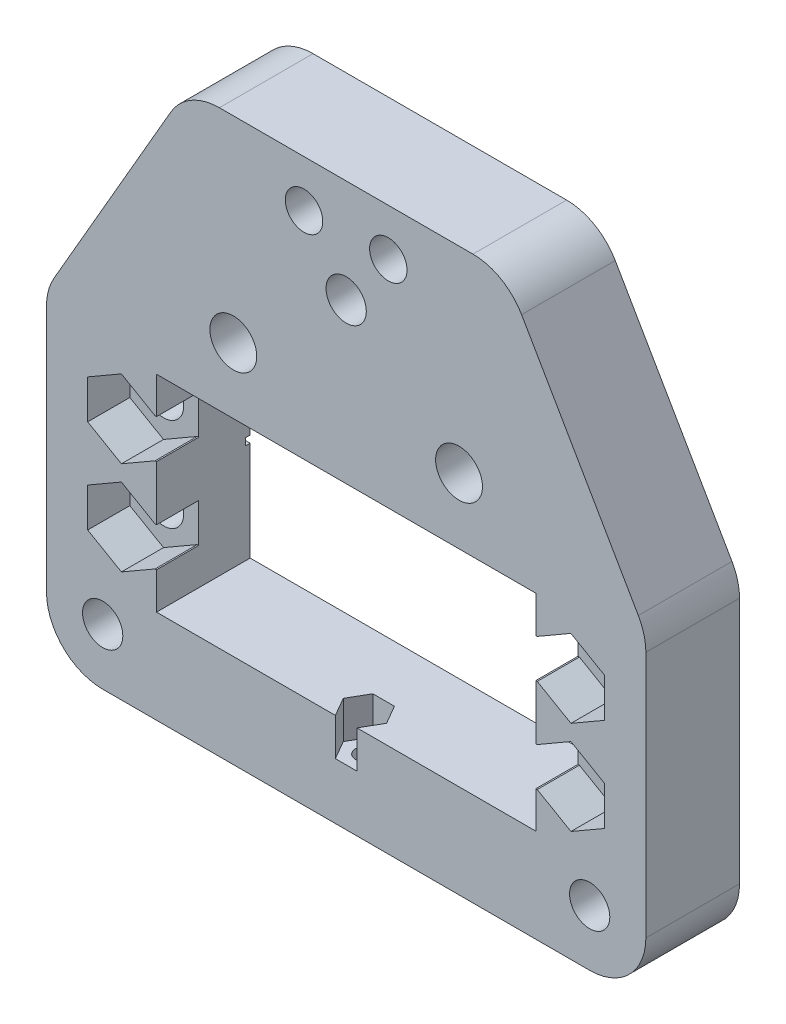
SolidWorks part; units mm, degrees
material "ABS"
ref_plane "Спереди" through (0, 0, 0) normal (0, 0, 1) x (1, 0, 0)
ref_plane "Сверху" through (0, 0, 0) normal (0, 1, 0) x (1, 0, 0)
ref_plane "Справа" through (0, 0, 0) normal (1, 0, 0) x (0, 0, -1)
sketch "Эскиз1" plane through (0, 0, 0) normal (0, 0, 1) x (1, 0, 0)
  line L0 (0, 0) -> (64, 0)
  line L1 (64, 0) -> (64, 34.0192)
  line L2 (64, 34.0192) -> (49, 60)
  line L3 (49, 60) -> (15, 60)
  line L4 (15, 60) -> (0, 34.02)
  line L5 (0, 34.02) -> (0, 0)
  dimension "D1" = 64
  dimension "D2" = 60
  dimension "D3" = 34
  dimension "D4" = 30
  dimension "D5" = 120
  dimension "D6" = 34.02
extrude "Бобышка-Вытянуть1" add sketch "Эскиз1" along normal blind 10 contours L0 L1 L2 L3 L4 L5
fillet "Скругление1" radius 6 6 edges at (49, 60, 5) (15, 60, 5) (0, 34.02, 5) (0, 0, 5) (64, 34.0192, 5) (64, 0, 5)
sketch "Эскиз2" plane through (0, 0, 10) normal (0, 0, 1) x (1, 0, 0)
  line L0 (11.75, 32) -> (52.25, 32)
  line L1 (52.25, 32) -> (52.25, 10)
  line L2 (52.25, 10) -> (11.75, 10)
  line L3 (11.75, 10) -> (11.75, 32)
  line L4 (64, 6) -> (64, 32.4115) construction
  line L5 (6, 0) -> (58, 0) construction
  dimension "D1" = 22
  dimension "D2" = 40.5
  dimension "D3" = 11.75
  dimension "D4" = 10
extrude "Вырез-Вытянуть1" cut sketch "Эскиз2" against normal through all
hole_wizard "Отверстия под штифты Ø4.0 мм1" positions "Эскиз3" profile "Эскиз4" hole size "Ø4.0" standard "Ansi Metric" end condition through all
sketch "Эскиз3" plane through (0, 0, 10) normal (0, 0, 1) x (1, 0, 0)
  line L0 (45.5359, 60) -> (18.4641, 60) construction
  line L1 (64, 6) -> (64, 32.4115) construction
  line L2 (32, 62.7032) -> (32, 49.5714) construction
  point P0 (27.4999, 55)
  point P2 (36.5, 55)
  point P13 (32, 60)
  dimension "D1" = 5
  dimension "D2" = 27.5
sketch "Эскиз4" plane through (27.4999, 55, 10) normal (1, 0, 0) x (0, -1, 0)
  line L0 (0, 0) -> (0, 10)
  line L1 (0, 10) -> (2, 10)
  line L2 (2, 10) -> (2, 0)
  line L5 (2, 0) -> (0, 0)
  line L11 (0, -6.35) -> (0, 13.871) construction
  dimension "Диаметр сквозного отверстия" = 4
  dimension "Глубина сквозного отверстия" = 10
hole_wizard "Отверстия под штифты Ø5.0 мм1" positions "Эскиз5" profile "Эскиз6" hole size "Ø5.0" standard "Ansi Metric" end condition through all
sketch "Эскиз5" plane through (0, 0, 10) normal (0, 0, 1) x (1, 0, 0)
  line L0 (45.5359, 60) -> (18.4641, 60) construction
  line L1 (64, 6) -> (64, 32.4115) construction
  line L2 (32, 62.5774) -> (32, 29.5493) construction
  point P0 (19.9499, 39)
  point P2 (44.05, 39)
  point P13 (32, 60)
  dimension "D1" = 21
  dimension "D2" = 19.95
sketch "Эскиз6" plane through (19.9499, 39, 10) normal (1, 0, 0) x (0, -1, 0)
  line L0 (0, 0) -> (0, 10)
  line L1 (0, 10) -> (2.5, 10)
  line L2 (2.5, 10) -> (2.5, 0)
  line L5 (2.5, 0) -> (0, 0)
  line L11 (0, -6.35) -> (0, 13.4589) construction
  dimension "Диаметр сквозного отверстия" = 5
  dimension "Глубина сквозного отверстия" = 10
hole_wizard "Сверло под метчик  спиральное M41" positions "Эскиз7" profile "Эскиз8" hole size "M4x0.7" standard "Ansi Metric" end condition through all
sketch "Эскиз7" plane through (0, 0, 10) normal (0, 0, 1) x (1, 0, 0)
  line L0 (52.25, 10) -> (52.25, 32) construction
  line L1 (52.25, 32) -> (11.75, 32) construction
  line L2 (32, 34.3929) -> (32, 8.0575) construction
  point P0 (56, 26)
  point P2 (56, 16)
  point P4 (8, 26)
  point P6 (8, 16)
  point P25 (32, 32)
  dimension "D1" = 3.75
  dimension "D2" = 6
  dimension "D3" = 10
sketch "Эскиз8" plane through (56, 26, 10) normal (1, 0, 0) x (0, -1, 0)
  line L0 (0, 0) -> (0, 10)
  line L1 (0, 10) -> (2.15, 10)
  line L2 (2.15, 10) -> (2.15, 0)
  line L5 (2.15, 0) -> (0, 0)
  line L11 (0, -6.35) -> (0, 14.6481) construction
  dimension "Диаметр сквозного отверстия" = 4.3
  dimension "Глубина сквозного отверстия" = 10
sketch "Эскиз9" plane through (0, 0, 10) normal (0, 0, -1) x (-1, 0, 0)
  line L0 (-56, 30.803) -> (-56, 10.8409) construction
  line L1 (-56, 30.1569) -> (-59.6, 28.0785)
  line L2 (-59.6, 28.0785) -> (-59.6, 23.9215)
  line L3 (-59.6, 23.9215) -> (-56, 21.8431)
  line L4 (-56, 21.8431) -> (-52.4, 23.9215)
  line L5 (-52.4, 23.9215) -> (-52.4, 28.0785)
  line L6 (-52.4, 28.0785) -> (-56, 30.1569)
  line L7 (-56, 20.1569) -> (-59.6, 18.0785)
  line L8 (-59.6, 18.0785) -> (-59.6, 13.9215)
  line L9 (-59.6, 13.9215) -> (-56, 11.8431)
  line L10 (-56, 11.8431) -> (-52.4, 13.9215)
  line L11 (-52.4, 13.9215) -> (-52.4, 18.0785)
  line L12 (-52.4, 18.0785) -> (-56, 20.1569)
  line L13 (-8, 30.1569) -> (-11.6, 28.0785)
  line L14 (-11.6, 28.0785) -> (-11.6, 23.9215)
  line L15 (-11.6, 23.9215) -> (-8, 21.8431)
  line L16 (-8, 21.8431) -> (-4.4, 23.9215)
  line L17 (-4.4, 23.9215) -> (-4.4, 28.0785)
  line L18 (-4.4, 28.0785) -> (-8, 30.1569)
  line L19 (-8, 20.1569) -> (-11.6, 18.0785)
  line L20 (-11.6, 18.0785) -> (-11.6, 13.9215)
  line L21 (-11.6, 13.9215) -> (-8, 11.8431)
  line L22 (-8, 11.8431) -> (-4.4, 13.9215)
  line L23 (-4.4, 13.9215) -> (-4.4, 18.0785)
  line L24 (-4.4, 18.0785) -> (-8, 20.1569)
  line L25 (-8, 30.803) -> (-8, 11.1079) construction
  circle A0 centre (-56, 26) radius 3.6 construction
  circle A1 centre (-56, 16) radius 3.6 construction
  circle A2 centre (-8, 26) radius 3.6 construction
  circle A3 centre (-8, 16) radius 3.6 construction
  dimension "D1" = 7.2
  dimension "D2" = 7.2
  dimension "D3" = 7.2
  dimension "D4" = 7.2
  dimension "D5" = 60
  dimension "D6" = 60
  dimension "D7" = 60
  dimension "D8" = 60
extrude "Вырез-Вытянуть4" cut sketch "Эскиз9" along normal blind 4.5
sketch "Эскиз12" plane through (0, 10, 0) normal (0, 1, 0) x (1, 0, 0)
  line L0 (32, 0.39) -> (32, -4.7781) construction
  line L7 (45.5359, 0) -> (18.4641, 0) construction
  line L9 (34.3094, -8) -> (33.1547, -6)
  line L10 (33.1547, -6) -> (30.8453, -6)
  line L11 (30.8453, -6) -> (29.6906, -8)
  line L12 (29.6906, -8) -> (30.8453, -10)
  line L13 (30.8453, -10) -> (33.1547, -10)
  line L14 (33.1547, -10) -> (34.3094, -8)
  circle A1 centre (32, -8) radius 2 construction
  point P12 (32, 0)
  dimension "D1" = 4
  dimension "D2" = 8
  dimension "D3" = 30
hole_wizard "Сверло под метчик  спиральное M42" positions "Эскиз16" profile "Эскиз17" hole size "M4x0.7" standard "Ansi Metric" end condition through all
sketch "Эскиз16" plane through (0, 0, 10) normal (0, 0, 1) x (1, 0, 0)
  line L0 (45.5359, 60) -> (18.4641, 60) construction
  line L1 (64, 6) -> (64, 32.4115) construction
  line L2 (6, 0) -> (58, 0) construction
  line L3 (32, -2.539) -> (32, 12.8188) construction
  point P0 (32, 49)
  point P2 (6, 6)
  point P4 (58, 6)
  point P19 (32, 0)
  dimension "D1" = 11
  dimension "D2" = 32
  dimension "D3" = 6
  dimension "D4" = 6
sketch "Эскиз17" plane through (32, 49, 10) normal (1, 0, 0) x (0, -1, 0)
  line L0 (0, 0) -> (0, 10)
  line L1 (0, 10) -> (2.15, 10)
  line L2 (2.15, 10) -> (2.15, 0)
  line L5 (2.15, 0) -> (0, 0)
  line L11 (0, -6.35) -> (0, 15.6845) construction
  dimension "Диаметр сквозного отверстия" = 4.3
  dimension "Глубина сквозного отверстия" = 10
sketch "Эскиз18" plane through (0, 0, 0) normal (0, 0, -1) x (-1, 0, 0)
  line L0 (-32, 53.874) -> (-32, 44.3135) construction
  line L1 (-32, 53.1569) -> (-35.6, 51.0785)
  line L2 (-35.6, 51.0785) -> (-35.6, 46.9215)
  line L3 (-35.6, 46.9215) -> (-32, 44.8431)
  line L4 (-32, 44.8431) -> (-28.4, 46.9215)
  line L5 (-28.4, 46.9215) -> (-28.4, 51.0785)
  line L6 (-28.4, 51.0785) -> (-32, 53.1569)
  line L7 (-58, 10.1569) -> (-61.6, 8.0785)
  line L8 (-61.6, 8.0785) -> (-61.6, 3.9215)
  line L9 (-61.6, 3.9215) -> (-58, 1.8431)
  line L10 (-58, 1.8431) -> (-54.4, 3.9215)
  line L11 (-54.4, 3.9215) -> (-54.4, 8.0785)
  line L12 (-54.4, 8.0785) -> (-58, 10.1569)
  line L13 (-6, 10.1569) -> (-9.6, 8.0785)
  line L14 (-9.6, 8.0785) -> (-9.6, 3.9215)
  line L15 (-9.6, 3.9215) -> (-6, 1.8431)
  line L16 (-6, 1.8431) -> (-2.4, 3.9215)
  line L17 (-2.4, 3.9215) -> (-2.4, 8.0785)
  line L18 (-2.4, 8.0785) -> (-6, 10.1569)
  line L19 (-58, 11.3834) -> (-58, 0.9026) construction
  line L20 (-6, 11.3834) -> (-6, 0.9026) construction
  circle A0 centre (-32, 49) radius 3.6 construction
  circle A1 centre (-58, 6) radius 3.6 construction
  circle A2 centre (-6, 6) radius 3.6 construction
  dimension "D1" = 7.2
  dimension "D2" = 7.2
  dimension "D3" = 7.2
  dimension "D4" = 60
  dimension "D5" = 60
  dimension "D6" = 60
extrude "Вырез-Вытянуть7" cut sketch "Эскиз18" against normal blind 3.2
sketch "Эскиз19" plane through (52.25, 0, 0) normal (-1, 0, 0) x (0, 0, 1)
  line L0 (10, 28.0785) -> (5.5, 28.0785)
  line L1 (10, 10) -> (10, 32) construction
  line L2 (5.5, 28.0785) -> (5.5, 23.9215)
  line L3 (5.5, 23.9215) -> (10, 23.9215)
  line L4 (10, 23.9215) -> (10, 28.0785)
  dimension "D1" = 4.5
extrude "Вырез-Вытянуть13" cut sketch "Эскиз19" against normal blind 0.15 contours L3 L4 L0 L2
sketch "Эскиз21" plane through (11.75, 0, 0) normal (1, 0, 0) x (0, 0, -1)
  line L0 (-10, 28.0785) -> (-5.5, 28.0785)
  line L1 (-10, 32) -> (-10, 10) construction
  line L2 (-5.5, 28.0785) -> (-5.5, 23.9215)
  line L3 (-5.5, 23.9215) -> (-10, 23.9215)
  line L4 (-10, 23.9215) -> (-10, 28.0785)
  dimension "D1" = 4.5
extrude "Вырез-Вытянуть14" cut sketch "Эскиз21" against normal blind 0.15
sketch "Эскиз22" plane through (52.25, 0, 0) normal (-1, 0, 0) x (0, 0, 1)
  line L0 (10, 18.0785) -> (5.5, 18.0785)
  line L1 (10, 10) -> (10, 23.9215) construction
  line L2 (5.5, 18.0785) -> (5.5, 13.9215)
  line L3 (5.5, 13.9215) -> (10, 13.9215)
  line L4 (10, 13.9215) -> (10, 18.0785)
  dimension "D1" = 4.5
extrude "Вырез-Вытянуть15" cut sketch "Эскиз22" against normal blind 0.15
sketch "Эскиз23" plane through (11.75, 0, 0) normal (1, 0, 0) x (0, 0, -1)
  line L0 (-10, 18.0785) -> (-5.5, 18.0785)
  line L1 (-10, 23.9215) -> (-10, 10) construction
  line L2 (-5.5, 18.0785) -> (-5.5, 13.9215)
  line L3 (-5.5, 13.9215) -> (-10, 13.9215)
  line L4 (-10, 13.9215) -> (-10, 18.0785)
  dimension "D1" = 4.5
extrude "Вырез-Вытянуть16" cut sketch "Эскиз23" against normal blind 0.15
extrude "Вырез-Вытянуть17" cut sketch "Эскиз12" against normal blind 4 contours L12 L13 L14 L9 L10 L11
hole_wizard "Сверло под метчик  спиральное M2.21" positions "Эскиз24" profile "Эскиз25" hole size "M2.2x0.45" standard "Ansi Metric"
sketch "Эскиз24" plane through (0, 0, 0) normal (0, -1, 0) x (-1, 0, 0)
  line L0 (-6, 0) -> (-58, 0) construction
  line L1 (-6, -10) -> (-6, 0) construction
  point P0 (-32, -8)
  dimension "D1" = 8
  dimension "D2" = 26
sketch "Эскиз25" plane through (32, 0, 8) normal (1, 0, 0) x (0, 0, -1)
  line L0 (0, 0) -> (0, 10.6009)
  line L1 (0, 10.6009) -> (1, 10)
  line L2 (1, 10) -> (1, 0)
  line L5 (1, 0) -> (0, 0)
  line L10 (0, 10.6009) -> (-1, 10) construction
  line L11 (0, -4.9654) -> (0, 14.7206) construction
  dimension "Диаметр отверстия" = 2
  dimension "Глубина отверстия" = 10
  dimension "Угол заточки сверла" = 118
sketch "Эскиз26" plane through (0, 0, 0) normal (0, 0, -1) x (-1, 0, 0)
  line L0 (-1008.75, 26) -> (48991.25, 26) construction
  line L1 (-1008.75, 16) -> (48991.25, 16) construction
  line L2 (-995.7251, 21.75) -> (49004.2749, 21.75) construction
  line L3 (-993.8158, 20.25) -> (49006.1842, 20.25) construction
  line L4 (-8, -974) -> (-8, 49026) construction
  line L5 (-5, -971.552) -> (-5, 49028.448) construction
  line L6 (-12, -970.5921) -> (-12, 49029.4079) construction
  line L7 (-1009.25, 21) -> (48990.75, 21) construction
  line L8 (-12, 20.25) -> (-5, 20.25)
  line L9 (-12, 20.25) -> (-12, 21.75)
  line L10 (-12, 21.75) -> (-5, 21.75)
  line L11 (-5, 20.25) -> (-5, 21.75)
  line L12 (-12, 20.25) -> (-5, 21.75) construction
  line L13 (-12, 21.75) -> (-5, 20.25) construction
  line L14 (-6, 0) -> (-58, 0) construction
  point P20 (-8.5, 21)
  dimension "D1" = 4.25
  dimension "D2" = 4.25
  dimension "D3" = 3
  dimension "D4" = 4
  dimension "D5" = 7
  dimension "D6" = 1.5
  dimension "D7" = 21
ref_plane "Плоскость1" through (0, 21, 0) normal (0, 1, 0) x (1, 0, 0)
sketch "Эскиз29" plane through (0, 21, 0) normal (0, 1, 0) x (1, 0, 0)
  line L0 (12.75, -1000) -> (12.75, 49000) construction
  line L1 (5.75, 0) -> (49815.4849, 4357.7871) construction
  line L2 (0, -1005.7303) -> (0, 48994.2697) construction
  line L3 (5.75, -1000) -> (5.75, 49000) construction
  line L4 (12, 0) -> (5, 0) construction
  line L10 (64, -1006.9199) -> (64, 48993.0801) construction
  line L12 (32, -998.6843) -> (32, 49001.3157) construction
  line L17 (51.25, 0) -> (51.25, -0.6124)
  line L18 (51.25, -0.6124) -> (58.25, 0)
  line L19 (58.25, 0) -> (51.25, 0)
  line L20 (5.75, 0) -> (12.75, 0)
  line L21 (12.75, -0.6124) -> (5.75, 0)
  line L22 (12.75, 0) -> (12.75, -0.6124)
  dimension "D1" = 5
  dimension "D3" = 32
  dimension "D4" = 64
sketch "Эскиз30" plane through (0, 0, 0) normal (0, 0, -1) x (-1, 0, 0)
  line L0 (-64, -972.7365) -> (-64, 49027.2635) construction
  line L2 (0, -971.7183) -> (0, 49028.2817) construction
  line L4 (-32, -971.4637) -> (-32, 49028.5363) construction
  line L5 (-11.75, 32) -> (-11.75, 10) construction
  dimension "D1" = 32
  dimension "D2" = 32
  dimension "D3" = 20.25
extrude "Вырез-Вытянуть19" cut sketch "Эскиз29" against normal mid plane 0.75 contours L21 L20 L22
extrude "Вырез-Вытянуть20" cut sketch "Эскиз29<3>" against normal mid plane 0.75 contours L18 L19 L17
sketch "Эскиз29<3>" plane through (0, 21, 0) normal (0, 1, 0) x (1, 0, 0) same geometry as "Эскиз29"
